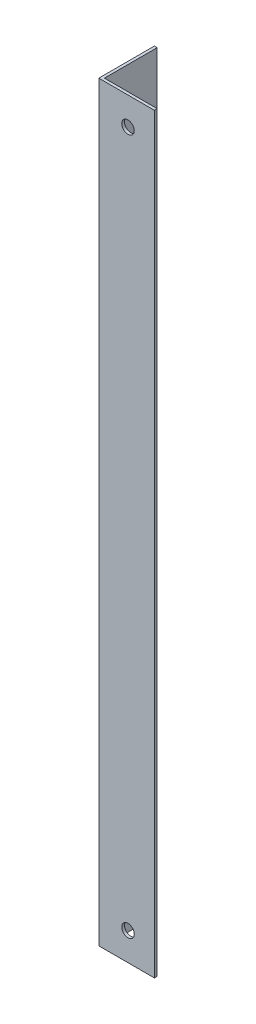
SolidWorks part; units mm, degrees
material "1060 Сплав"
ref_plane "Спереди" through (0, 0, 0) normal (0, 0, 1) x (1, 0, 0)
ref_plane "Сверху" through (0, 0, 0) normal (0, 1, 0) x (1, 0, 0)
ref_plane "Справа" through (0, 0, 0) normal (1, 0, 0) x (0, 0, -1)
sketch "Эскиз1" plane through (0, 0, 0) normal (0, 1, 0) x (1, 0, 0)
  line L0 (0, 0) -> (0, 20)
  line L1 (0, 20) -> (1, 20)
  line L2 (1, 20) -> (1, 1)
  line L3 (1, 1) -> (20, 1)
  line L4 (20, 1) -> (20, 0)
  line L5 (20, 0) -> (0, 0)
  dimension "D1" = 1
  dimension "D2" = 20
extrude "Бобышка-Вытянуть1" add sketch "Эскиз1" along normal blind 270
sketch "Эскиз2" plane through (1, 0, 0) normal (1, 0, 0) x (0, 0, -1)
  circle A0 centre (10.5, 29.5) radius 2.25 construction
  circle A1 centre (10.5, 29.5) radius 2.25
extrude "Вырез-Вытянуть1" cut sketch "Эскиз2" against normal through all
sketch "Эскиз3" plane through (0, 0, -1) normal (0, 0, -1) x (-1, 0, 0)
  line L0 (-10.5, 0) -> (-10.5, 10) construction
  line L1 (-20, 0) -> (-1, 0) construction
  circle A0 centre (-10.5, 10) radius 2.25
  dimension "D2" = 4.5
  dimension "D1" = 10
extrude "Вырез-Вытянуть2" cut sketch "Эскиз3" against normal through all
sketch "Эскиз4" plane through (0, 0, -1) normal (0, 0, -1) x (-1, 0, 0)
  line L0 (-10.5, 270) -> (-10.5, 260) construction
  line L1 (-20, 270) -> (-1, 270) construction
  circle A0 centre (-10.5, 260) radius 2.25
  dimension "D2" = 4.5
  dimension "D1" = 10
extrude "Вырез-Вытянуть3" cut sketch "Эскиз4" against normal through all
sketch "Эскиз5" plane through (1, 0, 0) normal (1, 0, 0) x (0, 0, -1)
  circle A0 centre (10.5, 180.5) radius 2.25 construction
  circle A1 centre (10.5, 180.5) radius 2.25
extrude "Вырез-Вытянуть4" cut sketch "Эскиз5" against normal through all
